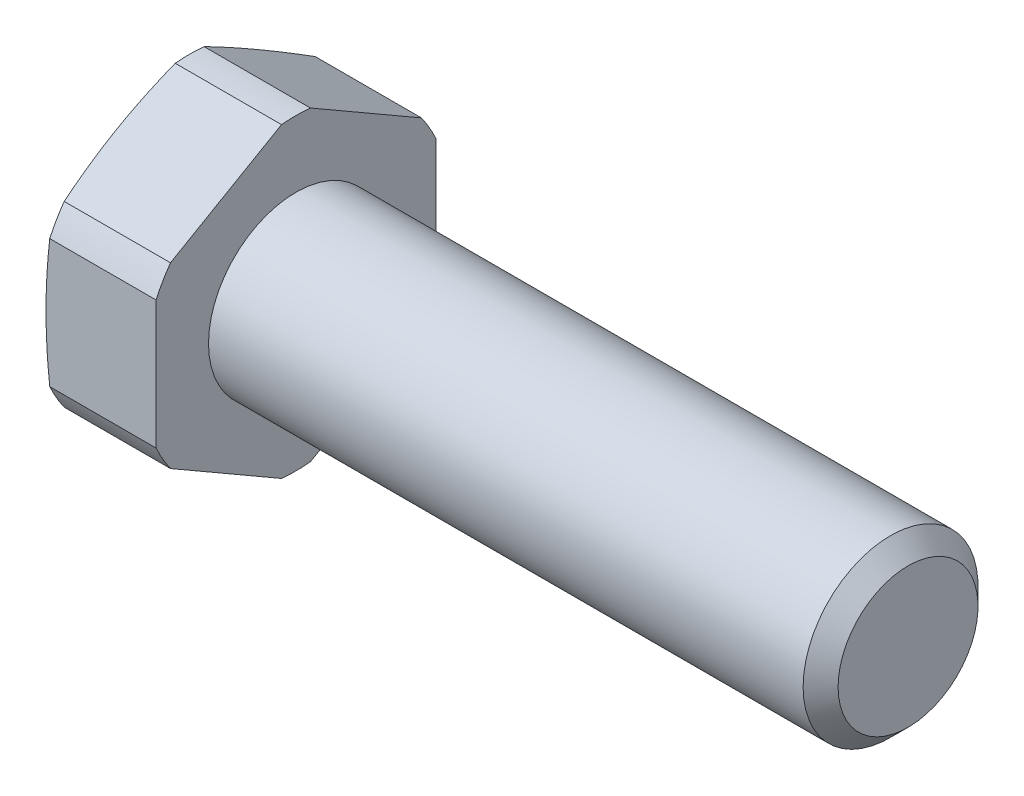
SolidWorks part; units mm, degrees
material "AISI 1020"
ref_plane "Спереди" through (0, 0, 0) normal (0, 0, 1) x (1, 0, 0)
ref_plane "Сверху" through (0, 0, 0) normal (0, 1, 0) x (1, 0, 0)
ref_plane "Справа" through (0, 0, 0) normal (1, 0, 0) x (0, 0, -1)
sketch "Эскиз1" plane through (0, 0, 0) normal (0, 0, 1) x (1, 0, 0)
  line L0 (-1000, 0) -> (49000, 0) construction
  line L1 (-6.4, 0) -> (-6.4, 7.6)
  line L2 (-6.4, 7.6) -> (-6.0785, 8.8)
  line L3 (-6.0785, 8.8) -> (0, 8.8)
  line L4 (0, 8.8) -> (0, 5)
  line L5 (0, 5) -> (34, 5)
  line L6 (35, 4) -> (35, 0)
  line L7 (35, 5) -> (35.75, 6.299) construction
  line L8 (35.75, 6.299) -> (36.5, 5) construction
  line L9 (36.5, 5) -> (35, 5) construction
  line L10 (35.75, 6.299) -> (35.75, 5) construction
  line L11 (35.75, 6.299) -> (9.75, 6.299) construction
  line L12 (34, 5) -> (35, 4)
  line L13 (35, 5) -> (34.5, 4.5) construction
  line L14 (-6.4, 7.6) -> (-22.4, 7.6) construction
  line L15 (-6.4, 0) -> (35, 0)
  dimension "D1" = 1
  dimension "D2" = 15
revolve "Повернуть1" add sketch "Эскиз1" angle 360 about L0
cosmetic thread "Условное изображение резьбы1" parameters "D1"=26, "D2"=7.4019
sketch "Эскиз2" plane through (-6.4, 0, 0) normal (-1, 0, 0) x (0, 0, 1)
  line L1 (0, 9.2376) -> (-8, 4.6188)
  line L2 (-8, 4.6188) -> (-8, -4.6188)
  line L3 (-8, -4.6188) -> (0, -9.2376)
  line L4 (0, -9.2376) -> (8, -4.6188)
  line L5 (8, -4.6188) -> (8, 4.6188)
  line L6 (8, 4.6188) -> (0, 9.2376)
  circle A0 centre (0, 0) radius 8 construction
  dimension "D1" = 16
extrude "Вырез-Вытянуть1" cut sketch "Эскиз2" against normal up to surface (41.4 mm away) flip side to cut up to face at (35, 0, 4)
equation "\"D1@Эскиз1\"=\"_d_@Эскиз1\"/10"
equation "\"D@Эскиз1\"=\"S_@Эскиз1\"*0.95"
equation "\"D1@Эскиз2\"=\"S_@Эскиз1\""
equation "\"D1@Условное изображение резьбы1\"=\"b_@Эскиз1\""
equation "\"D2@Условное изображение резьбы1\"=\"_d_@Эскиз1\"-\"dr@Эскиз1\"*2"
